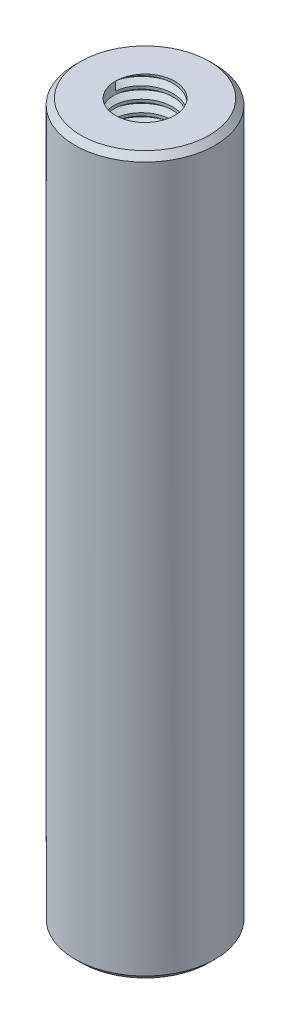
SolidWorks part; units mm, degrees
material "6061-T6 (SS)"
ref_plane "Alzado" through (0, 0, 0) normal (0, 0, 1) x (1, 0, 0)
ref_plane "Planta" through (0, 0, 0) normal (0, 1, 0) x (1, 0, 0)
ref_plane "Vista lateral" through (0, 0, 0) normal (1, 0, 0) x (0, 0, -1)
sketch "Croquis2" plane through (0, 0, 0) normal (0, 1, 0) x (1, 0, 0)
  circle A0 centre (0, 0) radius 4.7625
  dimension "D1" = 9.525
extrude "Saliente-Extruir1" add sketch "Croquis2" along normal mid plane 48.768
chamfer "Chaflán1" distance 0.3969 angle 45 2 edges at (0, -24.384, 4.7625) (0, 24.384, 4.7625)
sketch "Croquis3" plane through (0, 0, 0) normal (0, 1, 0) x (1, 0, 0)
  circle A0 centre (0, 0) radius 2.0193
  dimension "D1" = 4.0386
extrude "Tap Hole 1" cut sketch "Croquis3" against normal blind 19.05 from surface starting at face at (0, 24.384, 4.3656)
extrude "Tap Hole 2" cut sketch "Croquis3<2>" along normal blind 19.05 from surface starting at face at (0, -24.384, 4.3656)
sketch "Croquis3<2>" plane through (0, 0, 0) normal (0, 1, 0) x (1, 0, 0) same geometry as "Croquis3"
sketch "Croquis4" plane through (0, 0, 0) normal (0, 1, 0) x (1, 0, 0)
  circle A0 centre (0, 0) radius 2.4892
  dimension "D1" = 4.9784
extrude "Clearance Hole" [suppressed] cut sketch "Croquis4" against normal through all both and the other way through all
thread "Rosca1" pitch 0.7937 method cut profile "Perfil de rosca1" start angle 0, offset 0, length 0, pitch 0.7937, diameter 4.0386
ref_plane "Plano1" through (-2.0193, 24.384, 0) normal (0, 0, 1) x (-1, 0, 0)
sketch "Perfil de rosca1" plane through (-2.0193, 24.384, 0) normal (0, 0, 1) x (-1, 0, 0)
  line L0 (0, 0) -> (0, 0.7937) construction
  line L1 (0, 0) -> (0.4296, 0.248)
  line L2 (0.4296, 0.248) -> (0.4296, 0.3473)
  line L3 (0.4296, 0.3473) -> (0, 0.5953)
  line L4 (0.4296, 0.2977) -> (0, 0.2977) construction
  line L11 (0, 0) -> (0, 0.5953)
  point P2 (0, 0)
  dimension "Pitch" = 0.7937
  dimension "Profile_Angle" = 60
  dimension "Profile_Land" = 0.0992
  dimension "Profile_Height" = 0.4296
thread "Rosca2" pitch 0.7937 method cut profile "Perfil de rosca2" start angle 0, offset 0, length 0, pitch 0.7937, diameter 4.0386
ref_plane "Plano2" through (2.0193, -24.384, 0) normal (0, 0, 1) x (1, 0, 0)
sketch "Perfil de rosca2" plane through (2.0193, -24.384, 0) normal (0, 0, 1) x (1, 0, 0)
  line L0 (0, 0) -> (0, 0.7937) construction
  line L1 (0, 0) -> (0.4296, 0.248)
  line L2 (0.4296, 0.248) -> (0.4296, 0.3473)
  line L3 (0.4296, 0.3473) -> (0, 0.5953)
  line L4 (0.4296, 0.2977) -> (0, 0.2977) construction
  line L11 (0, 0) -> (0, 0.5953)
  point P2 (0, 0)
  dimension "Pitch" = 0.7937
  dimension "Profile_Angle" = 60
  dimension "Profile_Land" = 0.0992
  dimension "Profile_Height" = 0.4296
equation "\"OD\"= 0.375pulgadas"
equation "\"Largo\"= 1.92pulgadas"
equation "\"Tap Hole\"= IIF ( \"OD\" = 0.375pulgadas , 0.1590pulgadas , 0.201pulgadas )"
equation "\"Spacer Hole\"= IIF ( \"OD\" = 0.375pulgadas , 0.196pulgadas , 0.257pulgadas )"
equation "\"D1@Croquis2\"=\"OD\""
equation "\"D1@Saliente-Extruir1\"=\"Largo\""
equation "\"D1@Croquis3\"=\"Tap Hole\""
equation "\"D1@Croquis4\"=\"Spacer Hole\""
